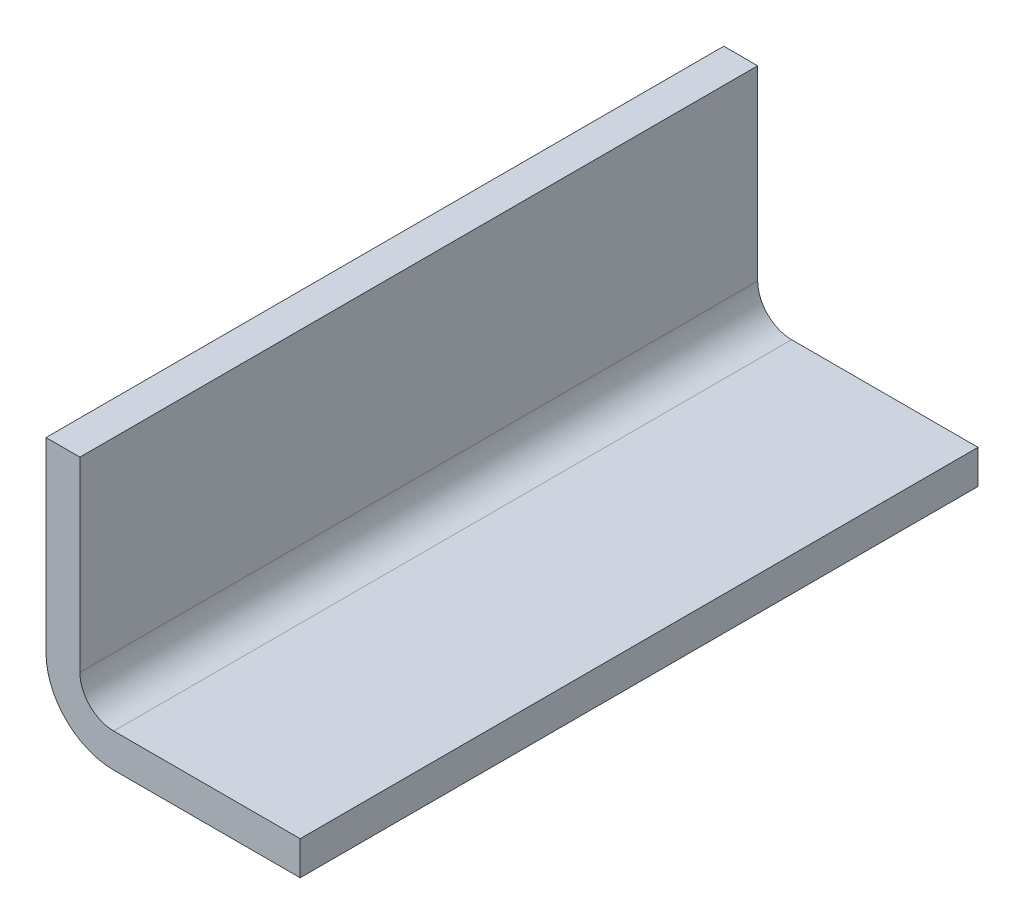
SolidWorks part; units mm, degrees
ref_plane "Front Plane" through (0, 0, 0) normal (0, 0, 1) x (1, 0, 0)
ref_plane "Top Plane" through (0, 0, 0) normal (0, 1, 0) x (1, 0, 0)
ref_plane "Right Plane" through (0, 0, 0) normal (1, 0, 0) x (0, 0, -1)
sketch "Sketch1" plane through (0, 0, 0) normal (0, 0, 1) x (1, 0, 0)
  line L0 (0, 4) -> (0, 15)
  line L1 (0, 15) -> (2, 15)
  line L2 (2, 15) -> (2, 4)
  line L3 (4, 2) -> (15, 2)
  line L4 (15, 2) -> (15, 0)
  line L5 (15, 0) -> (4, 0)
  arc A0 (2, 4) -> (4, 2) centre (4, 4) ccw
  arc A1 (0, 4) -> (4, 0) centre (4, 4) ccw
  point P11 (0, 0)
  dimension "D5" = 2
  dimension "D6" = 4
  dimension "D1" = 15
  dimension "D2" = 15
  dimension "D3" = 2
  dimension "D4" = 2
extrude "Boss-Extrude1" add sketch "Sketch1" along normal mid plane 40
